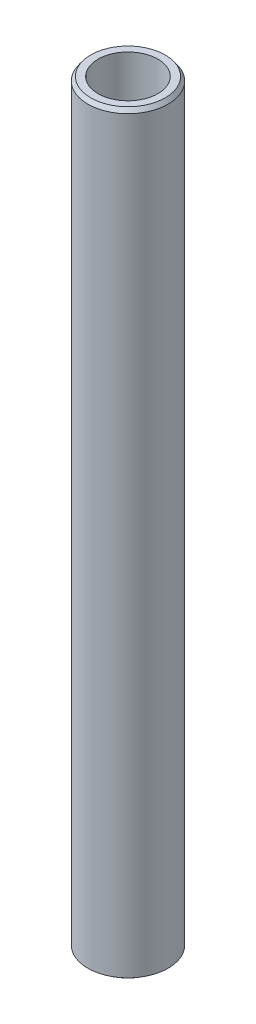
SolidWorks part; units mm, degrees
ref_plane "Front Plane" through (0, 0, 0) normal (0, 0, 1) x (1, 0, 0)
ref_plane "Top Plane" through (0, 0, 0) normal (0, 1, 0) x (1, 0, 0)
ref_plane "Right Plane" through (0, 0, 0) normal (1, 0, 0) x (0, 0, -1)
sketch "Sketch1" plane through (0, 0, 0) normal (0, 1, 0) x (1, 0, 0)
  circle A0 centre (0, 0) radius 25
  dimension "SHAFT_OD" = 50
extrude "Boss-Extrude1" add sketch "Sketch1" along normal blind 470.4168
sketch "Sketch2" plane through (0, 0, 0) normal (0, 1, 0) x (1, 0, 0)
  circle A0 centre (0, 0) radius 18.6426
  dimension "BORE_D" = 37.2852
extrude "Cut-Extrude1" cut sketch "Sketch2" along normal through all
chamfer "Chamfer1" distance 2.4791 angle 36.313 2 edges at (0, 470.4168, 25) (0, 0, 25) first distance on face at (0, 470.4168, 25) first distance on face at (0, 0, 18.6426)
